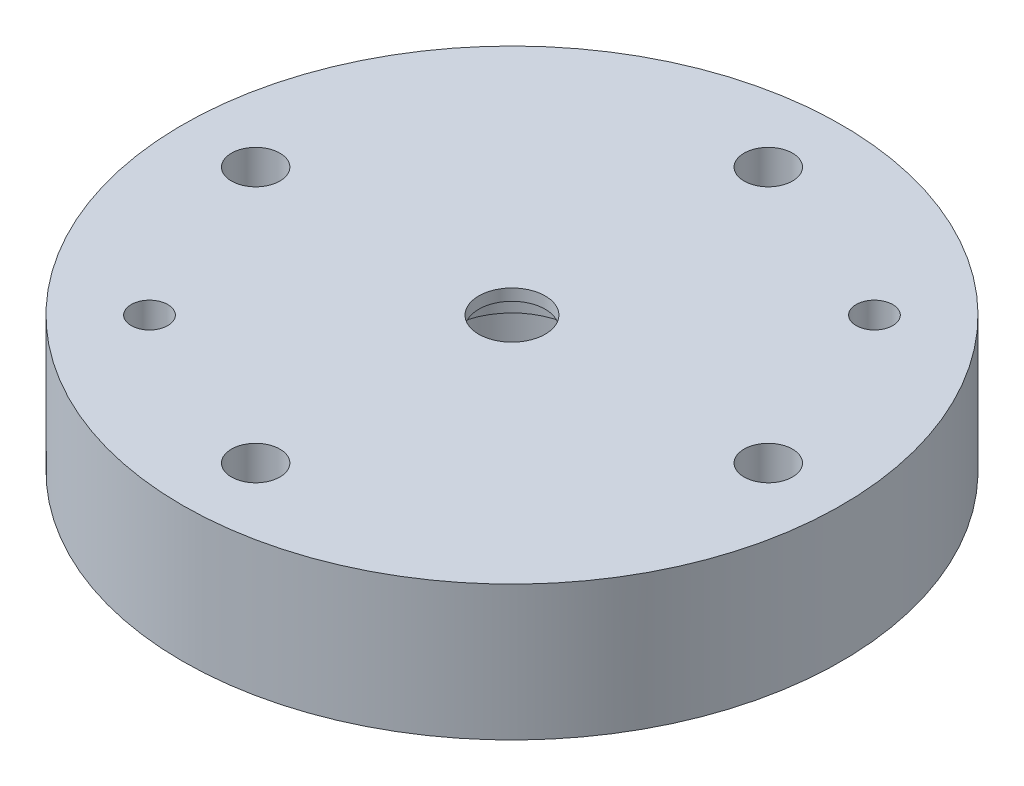
SolidWorks part; units mm, degrees
ref_plane "Front Plane" through (0, 0, 0) normal (0, 0, 1) x (1, 0, 0)
ref_plane "Top Plane" through (0, 0, 0) normal (0, 1, 0) x (1, 0, 0)
ref_plane "Right Plane" through (0, 0, 0) normal (1, 0, 0) x (0, 0, -1)
sketch "Sketch1" plane through (0, 0, 0) normal (0, 1, 0) x (1, 0, 0)
  circle A0 centre (0, 0) radius 57.15
  dimension "D1" = 114.3
extrude "seal seat hieght" add sketch "Sketch1" against normal blind 5.5372 contours A0
ref_plane "top end of seal" through (0, 0, 0) normal (0, 1, 0) x (1, 0, 0)
sketch "Sketch2" plane through (0, -5.5372, 0) normal (0, -1, 0) x (1, 0, 0)
  circle A1 centre (0, 0) radius 57.15
  circle A2 centre (0, 0) radius 57.15
  dimension "D1" = 0
extrude "seal diaphram hieght" add sketch "Sketch2" along normal blind 15.875
ref_plane "bottom end of seal" through (0, -21.4122, 0) normal (0, -1, 0) x (-1, 0, 0)
sketch "Sketch3" plane through (0, 0, 0) normal (0, 1, 0) x (1, 0, 0)
  circle A1 centre (0, 0) radius 57.15
  circle A2 centre (0, 0) radius 57.15
  dimension "D1" = 0
extrude "seal shoulder hieght" add sketch "Sketch3" along normal blind 2
sketch "Sketch4" plane through (0, -21.4122, 0) normal (0, -1, 0) x (1, 0, 0)
  circle A1 centre (0, 0) radius 57.15
  circle A2 centre (0, 0) radius 57.15
  dimension "D1" = 0
sketch "Sketch5" plane through (0, 0, 0) normal (0, 1, 0) x (1, 0, 0)
  circle A0 centre (0, 0) radius 11.1125
  dimension "D1" = 22.225
extrude "seal seat fit" cut sketch "Sketch5" against normal blind 5.5372
sketch "Sketch6" plane through (0, -21.4122, 0) normal (0, -1, 0) x (-1, 0, 0)
  circle A0 centre (0, 0) radius 12.7
  dimension "D1" = 25.4
sketch "Sketch7" plane through (0, 0, 0) normal (0, 1, 0) x (1, 0, 0)
  circle A0 centre (0, 0) radius 4.7625 construction
  circle A1 centre (0, 0) radius 5.7625
  dimension "D1" = 9.525
  dimension "D2" = 1
extrude "shaft clearance" cut sketch "Sketch7" along normal up to surface (2 mm away) up to face at (0, 2, 57.15)
sketch "bolt circle" plane through (0, 2, 0) normal (0, 1, 0) x (1, 0, 0)
  circle A0 centre (0, 0) radius 44.45 construction
  point P3 (-44.45, 0)
  point P4 (0, 44.45)
  point P5 (44.45, 0)
  point P6 (0, -44.45)
  dimension "D1" = 88.9
hole_wizard "M8 Clearance Hole1" positions "Sketch11" profile "Sketch12" hole size "M8" standard "ANSI Metric" end condition through all
sketch "Sketch11" plane through (0, 2, 0) normal (0, 1, 0) x (1, 0, 0)
  point P0 (-44.45, 0)
  point P3 (0, 44.45)
  point P6 (44.45, 0)
  point P9 (0, -44.45)
sketch "Sketch12" plane through (-44.45, 2, 0) normal (1, 0, 0) x (0, 0, 1)
  line L0 (0, 0) -> (0, 23.4122)
  line L1 (0, 23.4122) -> (4.2, 23.4122)
  line L2 (4.2, 23.4122) -> (4.2, 0)
  line L5 (4.2, 0) -> (0, 0)
  line L11 (0, -6.35) -> (0, 107.95) construction
  dimension "Thru Hole Dia." = 8.4
  dimension "Thru Hole Depth" = 23.4122
sketch "dowel hole positioning " plane through (0, 2, 0) normal (0, 1, 0) x (1, 0, 0)
  line L0 (0, 0) -> (53.8672, 0) construction
  line L1 (-31.4309, -31.4309) -> (31.4309, 31.4309) construction
  circle A0 centre (0, 0) radius 44.45 construction
  circle A1 centre (0, 0) radius 44.45 construction
  point P8 (0, 0)
  point P9 (31.4309, 31.4309)
  point P10 (-31.4309, -31.4309)
  dimension "D1" = 45
hole_wizard "1/4 (0.25) Press Dowel Hole1" positions "Sketch14" profile "Sketch15" hole size "1/4" standard "ANSI Inch" end condition through all
sketch "Sketch14" plane through (0, 2, 0) normal (0, 1, 0) x (1, 0, 0)
  point P0 (31.4309, 31.4309)
  point P3 (-31.4309, -31.4309)
sketch "Sketch15" plane through (31.4309, 2, -31.4309) normal (1, 0, 0) x (0, 0, 1)
  line L0 (0, 0) -> (0, 23.4122)
  line L1 (0, 23.4122) -> (3.175, 23.4122)
  line L2 (3.175, 23.4122) -> (3.175, 0)
  line L5 (3.175, 0) -> (0, 0)
  line L11 (0, -6.35) -> (0, 107.95) construction
  dimension "Thru Hole Dia." = 6.35
  dimension "Thru Hole Depth" = 23.4122
extrude "Cut-Extrude1" cut sketch "Sketch6" against normal up to surface (15.875 mm away) up to face at (0, -5.5372, 11.1125)
equation "\"seal seat height\"=5.5372"
equation "\"D1@seal seat hieght\" = \"seal seat height\""
equation "\"seal diaphram height\"=15.875"
equation "\"D1@seal diaphram hieght\" = \"seal diaphram height\""
equation "\"seal shoulder height\"=2"
equation "\"D1@seal shoulder hieght\" = \"seal shoulder height\""
equation "\"seal seat OD\"= .875in"
equation "\"D1@Sketch5\"=\"seal seat OD\""
equation "\"D1@seal seat fit\" = \"seal seat height\""
equation "\"seal diaphram clearance\"=25.4"
equation "\"D1@Sketch6\"=\"seal diaphram clearance\""
equation "\"seal ID\"=9.525"
equation "\"D1@Sketch7\"=\"seal ID\""
equation "\"bolt circle dia\"=88.9"
equation "\"D1@bolt circle\" = \"bolt circle dia\""
